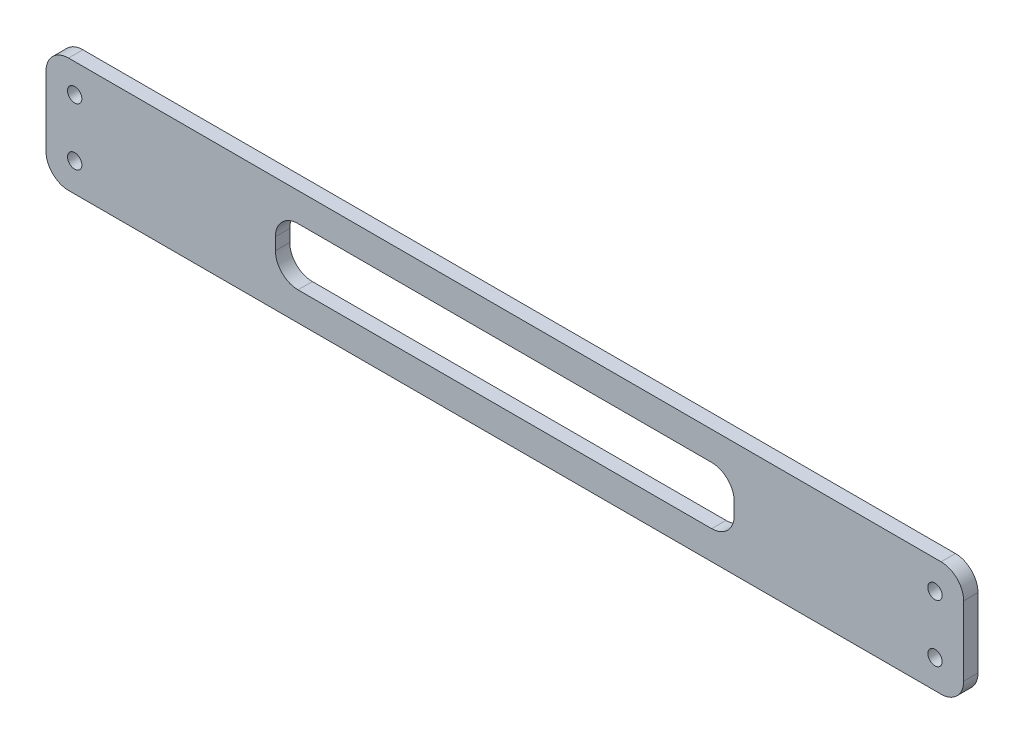
SolidWorks part; units mm, degrees
ref_plane "Front Plane" through (0, 0, 0) normal (0, 0, 1) x (1, 0, 0)
ref_plane "Top Plane" through (0, 0, 0) normal (0, 1, 0) x (1, 0, 0)
ref_plane "Right Plane" through (0, 0, 0) normal (1, 0, 0) x (0, 0, -1)
sketch "Sketch1" plane through (0, 0, 0) normal (0, 0, 1) x (1, 0, 0)
  line L3 (-203.2, -25.4) -> (203.2, -25.4)
  line L4 (-203.2, -25.4) -> (-203.2, 25.4)
  line L5 (-203.2, 25.4) -> (203.2, 25.4)
  line L6 (203.2, -25.4) -> (203.2, 25.4)
  line L7 (-203.2, -25.4) -> (203.2, 25.4) construction
  line L8 (-203.2, 25.4) -> (203.2, -25.4) construction
  point P0 (0, 0)
  dimension "D1" = 406.4
  dimension "D2" = 50.8
extrude "Boss-Extrude1" add sketch "Sketch1" along normal blind 6.35
sketch "Sketch2" plane through (0, 0, 6.35) normal (0, 0, 1) x (1, 0, 0)
  line L1 (-91.6, -12.7) -> (91.6, -12.7)
  line L2 (-101.6, -2.7) -> (-101.6, 2.7)
  line L3 (-91.6, 12.7) -> (91.6, 12.7)
  line L4 (101.6, -2.7) -> (101.6, 2.7)
  line L5 (-101.6, -12.7) -> (101.6, 12.7) construction
  line L6 (-101.6, 12.7) -> (101.6, -12.7) construction
  arc A0 (91.6, 12.7) -> (101.6, 2.7) centre (91.6, 2.7) cw
  arc A1 (91.6, -12.7) -> (101.6, -2.7) centre (91.6, -2.7) ccw
  arc A2 (-91.6, -12.7) -> (-101.6, -2.7) centre (-91.6, -2.7) cw
  arc A3 (-101.6, 2.7) -> (-91.6, 12.7) centre (-91.6, 2.7) cw
  point P0 (0, 0)
  dimension "D3" = 10
  dimension "D1" = 203.2
  dimension "D2" = 25.4
extrude "Cut-Extrude1" cut sketch "Sketch2" against normal blind 6.35
fillet "Fillet1" radius 10 4 edges at (203.2, -25.4, 3.175) (203.2, 25.4, 3.175) (-203.2, -25.4, 3.175) (-203.2, 25.4, 3.175)
sketch "Sketch3" plane through (0, 0, 6.35) normal (0, 0, 1) x (1, 0, 0)
  line L0 (193.2, 25.4) -> (-193.2, 25.4) construction
  line L1 (-203.2, 15.4) -> (-203.2, -15.4) construction
  line L2 (0, 0) -> (0, 58.4853) construction
  circle A0 centre (-190.5, 12.7) radius 3.175
  circle A1 centre (-190.5, -12.7) radius 3.175
  circle A2 centre (190.5, -12.7) radius 3.175
  circle A3 centre (190.5, 12.7) radius 3.175
  dimension "D1" = 6.35
  dimension "D2" = 6.35
  dimension "D3" = 25.4
  dimension "D4" = 12.7
  dimension "D5" = 12.7
  dimension "D6" = 12.7
extrude "Cut-Extrude2" cut sketch "Sketch3" against normal blind 6.35
